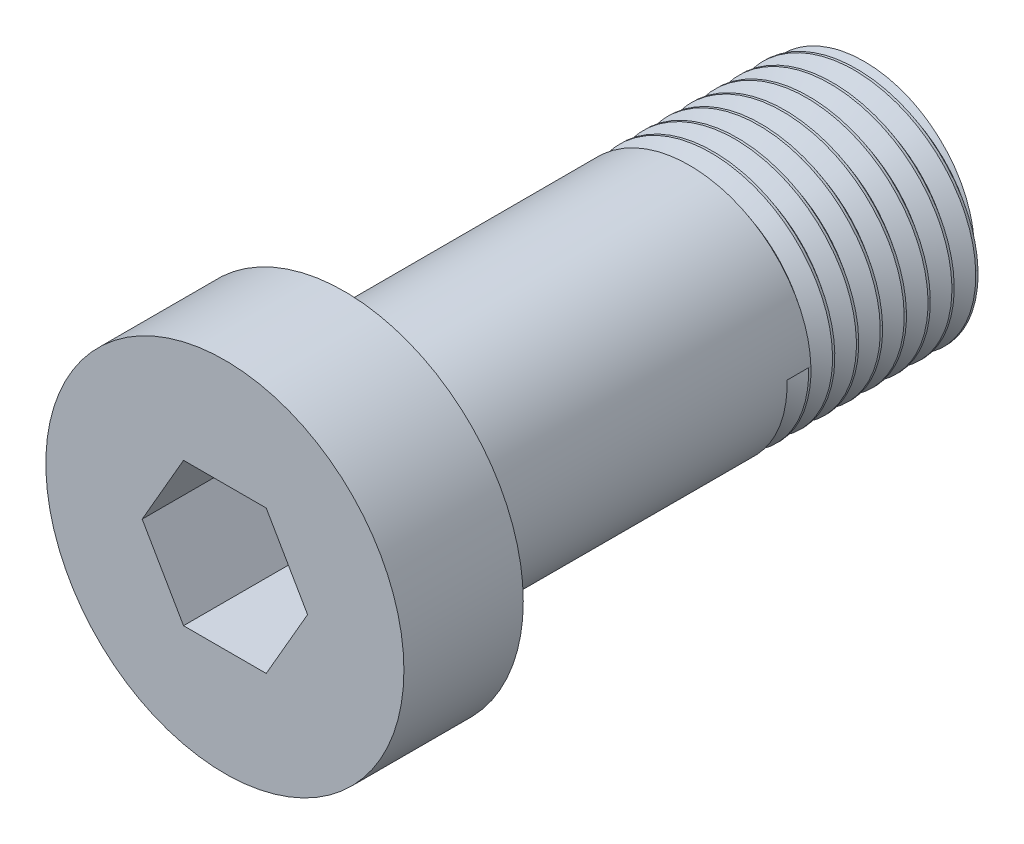
SolidWorks part; units mm, degrees
material "AISI 304"
ref_plane "Alzado" through (0, 0, 0) normal (0, 0, 1) x (1, 0, 0)
ref_plane "Planta" through (0, 0, 0) normal (0, 1, 0) x (1, 0, 0)
ref_plane "Vista lateral" through (0, 0, 0) normal (1, 0, 0) x (0, 0, -1)
ref_plane "Plano1" through (0, 0, 44.4) normal (0, 0, 1) x (1, 0, 0)
sketch "Sk_Cana" plane through (0, 0, 44.4) normal (0, 0, 1) x (1, 0, 0)
  circle A0 centre (-6, -26) radius 5
extrude "Cana" add sketch "Sk_Cana" along normal blind 22
ref_plane "Plano2" through (0, 0, 66.4) normal (0, 0, 1) x (1, 0, 0)
sketch "Sk_Cabeza" plane through (0, 0, 66.4) normal (0, 0, 1) x (1, 0, 0)
  line L0 (-2.5359, -26) -> (-4.2679, -23)
  line L1 (-4.2679, -23) -> (-7.7321, -23)
  line L2 (-7.7321, -23) -> (-9.4641, -26)
  line L3 (-9.4641, -26) -> (-7.7321, -29)
  line L4 (-7.7321, -29) -> (-4.2679, -29)
  line L5 (-4.2679, -29) -> (-2.5359, -26)
  circle A0 centre (-6, -26) radius 7.5
extrude "Cabeza" add sketch "Sk_Cabeza" along normal blind 5
ref_plane "Plano3" through (0, 0, 44.4) normal (0, 0, 1) x (1, 0, 0)
sketch "Sk_Helice_Rosca_M10x1" plane through (0, 0, 44.4) normal (0, 0, 1) x (1, 0, 0)
  circle A0 centre (-6, -26) radius 5
curve "Helice_Rosca_M10x1" pitch 1 height 8 radius 5 centre (-6, -26, 44.4) axis (0, 0, 1) start towards (1, 0, 0)
ref_plane "Plano5" through (0, -26, 0) normal (0, 1, 0) x (1, 0, 0)
sketch "Sk_perfil_Rosca_M10x1" plane through (0, -26, 0) normal (0, 1, 0) x (1, 0, 0)
  line L0 (-0.7, -43.7268) -> (-0.7, -45.0732)
  line L1 (-0.7, -45.0732) -> (-1.6134, -44.4)
  line L2 (-1.6134, -44.4) -> (-0.7, -43.7268)
sweep "Rosca_M10x1" cut profiles "Sk_perfil_Rosca_M10x1" path "Helice_Rosca_M10x1" align with end faces yes
